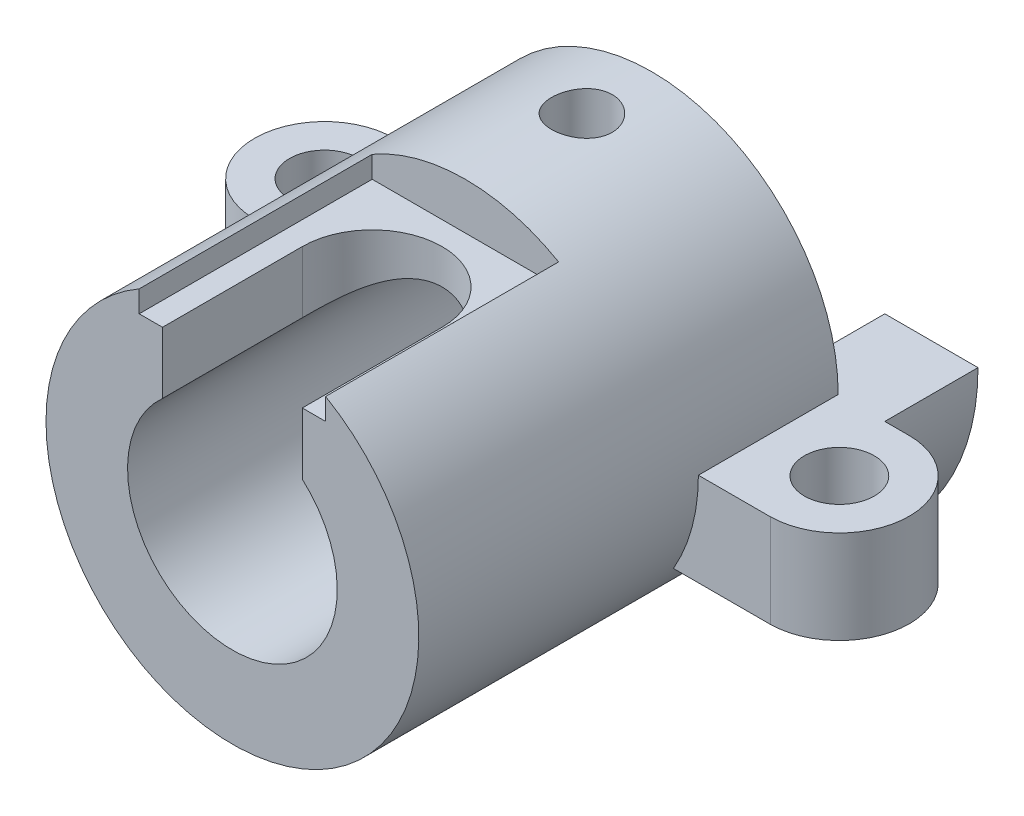
SolidWorks part; units mm, degrees
ref_plane "Front Plane" through (0, 0, 0) normal (0, 0, 1) x (1, 0, 0)
ref_plane "Top Plane" through (0, 0, 0) normal (0, 1, 0) x (1, 0, 0)
ref_plane "Right Plane" through (0, 0, 0) normal (1, 0, 0) x (0, 0, -1)
sketch "Sketch1" plane through (0, 0, 0) normal (0, 0, 1) x (1, 0, 0)
  line L0 (-50, 0) -> (-22.5, 0)
  line L1 (22.5, 0) -> (50, 0)
  arc A0 (-50, 0) -> (50, 0) centre (0, 0) ccw
  circle A1 centre (0, 0) radius 40
  circle A2 centre (0, 0) radius 30
  circle A3 centre (0, 0) radius 22.5
  point P9 (0, 0)
  dimension "D1" = 100
  dimension "D2" = 80
  dimension "D3" = 60
  dimension "D4" = 45
extrude "Boss-Extrude1" add sketch "Sketch1" along normal blind 90 contours A2 L1 A1 L0 | A2 L0 A1 L1 | A3 L1 A2 L0 | A3 L0 A2 L1 region at (0, 39.1056, 0) region at (-35, -0.8944, 0) region at (0, 29.3292, 0) region at (-26.25, -0.6708, 0)
extrude "Boss-Extrude2" add sketch "Sketch1<3>" against normal blind 20 contours A1 L0 A0 L1 | A2 L0 A1 L1 region at (-45, -1.118, 0) region at (-35, -0.8944, 0)
sketch "Sketch1<3>" plane through (0, 0, 0) normal (0, 0, 1) x (1, 0, 0) same geometry as "Sketch1"
sketch "Sketch3" plane through (0, 0, 0) normal (0, 1, 0) x (1, 0, 0)
  line L0 (40, 0) -> (50, 0) construction
  line L1 (34.4452, 0) -> (55, 0)
  line L2 (34.4452, 0) -> (34.4452, -30)
  line L3 (34.4452, -30) -> (55.4899, -30)
  line L5 (-40, 0) -> (40, 0) construction
  line L6 (0, 0) -> (0, -12.5074) construction
  line L7 (-34.4452, 0) -> (-34.4452, -30)
  line L8 (-34.4452, -30) -> (-55.4899, -30)
  line L9 (-34.4452, 0) -> (-55, 0)
  arc A0 (55.4899, -30) -> (55, 0) centre (55.2449, -15) ccw
  arc A1 (-55.4899, -30) -> (-55, 0) centre (-55.2449, -15) cw
  circle A2 centre (55.2449, -15) radius 7.5
  circle A3 centre (-55.2449, -15) radius 7.5
  dimension "D3" = 15
  dimension "D1" = 110
  dimension "D2" = 30
extrude "Boss-Extrude9" add sketch "Sketch3" against normal blind 20
ref_plane "Plane1" through (0, 40, 0) normal (0, 1, 0) x (1, 0, 0)
sketch "Sketch5" plane through (0, 40, 0) normal (0, 1, 0) x (1, 0, 0)
  line L0 (-40, -90) -> (40, -90) construction
  line L2 (-15, -60) -> (-15, -90)
  line L3 (-15, -90) -> (15, -90)
  line L4 (15, -60) -> (15, -90)
  line L5 (-20, -140) -> (20, -140)
  line L10 (-20, -140) -> (-20, -40)
  line L11 (20, -140) -> (20, -40)
  line L12 (-20, -40) -> (20, -40)
  line L13 (-20, -140) -> (20, -40) construction
  line L14 (20, -140) -> (-20, -40) construction
  arc A0 (15, -60) -> (-15, -60) centre (0, -60) ccw
  circle A1 centre (0, -15) radius 6.5
  point P8 (0, -90)
  point P9 (0, -90)
  point P12 (0, -90)
  point P14 (-20, -90)
  dimension "D1" = 30
  dimension "D5" = 13
  dimension "D2" = 30
  dimension "D3" = 40
  dimension "D4" = 50
  dimension "D6" = 15
  dimension "D7" = 10
extrude "Cut-Extrude1" cut sketch "Sketch5" against normal up to surface (23.2295 mm away) contours L4 A0 L2 L3 | A1 region at (0, 40, 68.9754) up to face at (22.5, 0, 90)
extrude "Cut-Extrude2" cut sketch "Sketch5<3>" against normal blind 10 contours L12 L10 L5 L11 A0 L4 L3 L2 region at (0, 40, 99.5948)
sketch "Sketch5<3>" plane through (0, 40, 0) normal (0, 1, 0) x (1, 0, 0) same geometry as "Sketch5"
hole_wizard "Ø2.0mm Dowel Hole1" positions "Sketch9" profile "Sketch8" hole size "Ø2.0" standard "ISO"
sketch "Sketch9" plane through (0, 0, -20) normal (0, 0, -1) x (-1, 0, 0)
  arc A0 (-34.641, -20) -> (34.641, -20) centre (0, 0) ccw construction
  point P0 (0, -40)
sketch "Sketch8" plane through (0, -40, -20) normal (1, 0, 0) x (0, 1, 0)
  line L0 (0, 0) -> (0, 19.1754)
  line L1 (0, 19.1754) -> (5.5, 16)
  line L2 (5.5, 16) -> (5.5, 0)
  line L5 (5.5, 0) -> (0, 0)
  line L10 (0, 19.1754) -> (-5.5, 16) construction
  line L11 (0, -6.35) -> (0, 107.95) construction
  dimension "Hole Dia." = 11
  dimension "Hole Depth" = 16
  dimension "Drill Angle" = 120
